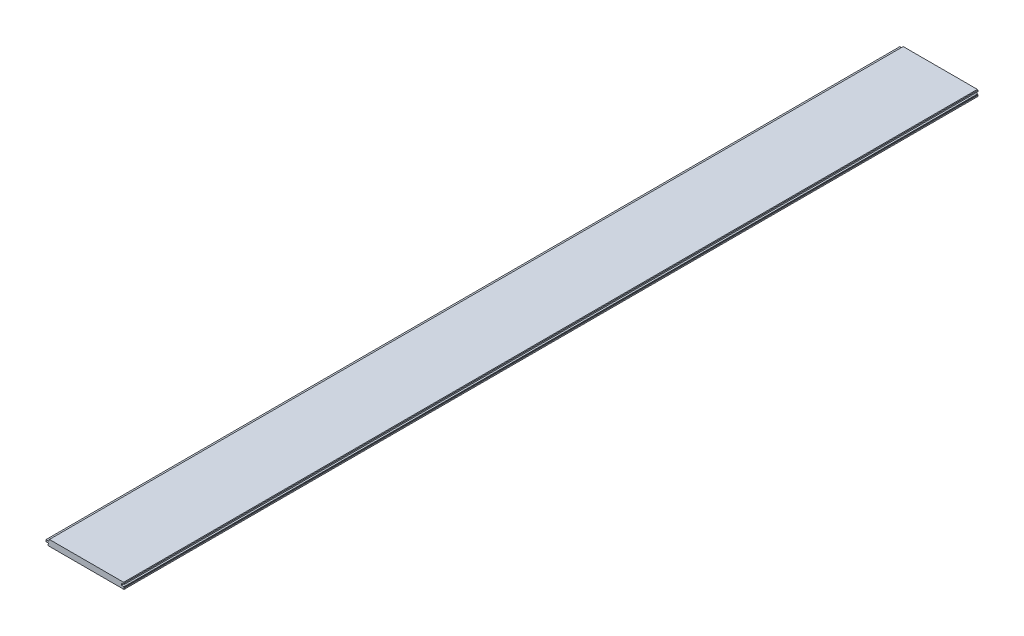
SolidWorks part; units mm, degrees
ref_plane "Front Plane" through (0, 0, 0) normal (0, 0, 1) x (1, 0, 0)
ref_plane "Top Plane" through (0, 0, 0) normal (0, 1, 0) x (1, 0, 0)
ref_plane "Right Plane" through (0, 0, 0) normal (1, 0, 0) x (0, 0, -1)
sketch "Sketch1" plane through (0, 0, 0) normal (0, 0, 1) x (1, 0, 0)
  line L0 (-93.1355, 2.9845) -> (-100.3745, 2.9845)
  line L1 (-95.1675, 7.5565) -> (95.1675, 7.5565)
  line L2 (-95.1675, 7.5565) -> (-95.1675, -7.5565)
  line L3 (-95.1675, -7.5565) -> (95.1675, -7.5565)
  line L4 (95.1675, 7.5565) -> (95.1675, -7.5565)
  line L5 (-95.1675, 7.5565) -> (95.1675, -7.5565) construction
  line L6 (-95.1675, -7.5565) -> (95.1675, 7.5565) construction
  line L7 (-100.3745, 2.9845) -> (-100.3745, -1.5875)
  line L8 (-100.3745, -1.5875) -> (-95.1675, -1.5875)
  line L9 (-95.1675, -1.5875) -> (-95.1675, -7.5565)
  line L10 (94.8372, 3.1242) -> (87.9158, 3.1242)
  line L11 (87.9158, 3.1242) -> (87.9158, -1.4986)
  line L12 (87.9158, -1.4986) -> (94.5324, -1.4986)
  line L13 (94.5324, -1.4986) -> (94.5324, -3.1115)
  line L14 (-93.1355, 2.9845) -> (-93.1355, 7.5565)
  line L15 (-93.1355, 6.2865) -> (-91.8654, 7.5565)
  line L16 (-95.1675, -1.5875) -> (-94.5324, -1.5875)
  line L17 (-94.5324, -1.5875) -> (-94.5324, -3.1115)
  line L18 (-94.5324, -3.1115) -> (-95.1675, -3.7465)
  line L19 (-94.5324, -7.5565) -> (-95.1675, -6.9215)
  line L20 (94.8372, 3.1242) -> (94.8372, 7.5565)
  line L21 (94.5324, -3.1115) -> (95.1675, -3.7465)
  line L22 (94.5324, -7.5565) -> (95.1675, -6.9215)
  line L23 (94.8372, 6.2865) -> (93.5672, 7.5565)
  dimension "D1" = 190.3349
  dimension "D2" = 15.113
  dimension "D3" = 9.144
  dimension "D4" = 7.239
  dimension "D5" = 4.572
  dimension "D6" = 5.207
  dimension "D7" = 6.0579
  dimension "D8" = 4.6228
  dimension "D9" = 0.635
  dimension "D10" = 6.9215
  dimension "D11" = 45
  dimension "D12" = 1.27
  dimension "D13" = 3.81
  dimension "D14" = 0.635
  dimension "D15" = 45
  dimension "D16" = 0.635
  dimension "D17" = 45
  dimension "D18" = 7.2517
  dimension "D19" = 1.27
extrude "Boss-Extrude1" add sketch "Sketch1" along normal mid plane 2133.6 contours L13 L12 L11 L10 L4 L1 L2 L8 L9 L3 | L7 L8 L2 L0 region at (-0.8274, -0.0306, 0) region at (-97.771, 0.6985, 0)
ref_plane "Plane1" through (0, 0, -1117.6) normal (0, 0, -1) x (-1, 0, 0)
sketch "Sketch2" plane through (0, 0, -1117.6) normal (0, 0, 1) x (1, 0, 0)
  line L0 (-94.5324, -7.5565) -> (94.5325, -7.5565) construction
  line L1 (-94.5324, -7.5565) -> (94.5325, -7.5565)
  point P2 (0, -7.5565)
